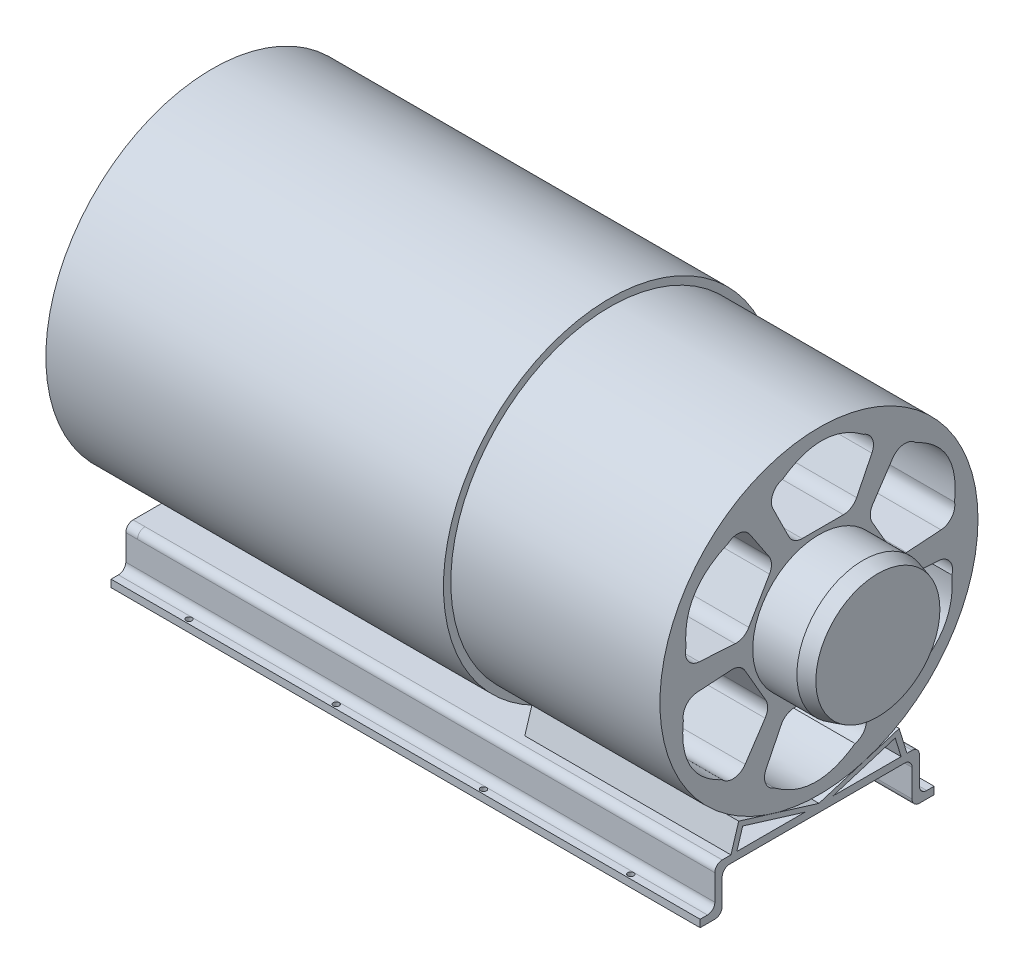
SolidWorks part; units mm, degrees
material "1060 Alloy"
ref_plane "Front Plane" through (0, 0, 0) normal (0, 0, 1) x (1, 0, 0)
ref_plane "Top Plane" through (0, 0, 0) normal (0, 1, 0) x (1, 0, 0)
ref_plane "Right Plane" through (0, 0, 0) normal (1, 0, 0) x (0, 0, -1)
sketch "Sketch1" plane through (0, 0, 0) normal (1, 0, 0) x (0, 0, -1)
  circle A0 centre (0, 0) radius 113
  dimension "D1" = 226
extrude "Boss-Extrude1" add sketch "Sketch1" against normal blind 412
sketch "Sketch2" plane through (0, 0, 0) normal (1, 0, 0) x (0, 0, -1)
  circle A0 centre (0, 0) radius 108
  circle A1 centre (0, 0) radius 113
  dimension "D1" = 216
extrude "Cut-Extrude1" cut sketch "Sketch2" against normal blind 142
sketch "Sketch3" plane through (0, 0, 0) normal (1, 0, 0) x (0, 0, -1)
  circle A0 centre (0, 0) radius 45
  dimension "D1" = 90
extrude "Boss-Extrude2" add sketch "Sketch3" along normal blind 40
chamfer "Chamfer1" distance 10 angle 16 1 edges at (40, 0, -45) first distance on face at (40, 0, -45)
sketch "Sketch4" plane through (0, 0, 0) normal (1, 0, 0) x (0, 0, -1)
  line L0 (-31.2402, 75.8787) -> (-20.392, 53.9645)
  line L1 (-11.43, 48.401) -> (16.6248, 48.401)
  line L2 (25.5919, 53.9748) -> (35.9576, 74.9748)
  line L3 (50.0927, 64.9942) -> (36.5386, 44.6422)
  line L4 (36.2015, 34.0991) -> (50.2288, 9.803)
  line L5 (59.5394, 4.8242) -> (82.9089, 6.3472)
  line L6 (81.333, -10.8845) -> (56.9306, -9.3223)
  line L7 (47.6314, -14.3018) -> (33.6041, -38.5979)
  line L8 (33.9476, -49.1506) -> (46.9513, -68.6276)
  line L9 (31.2402, -75.8787) -> (20.392, -53.9645)
  line L10 (11.43, -48.401) -> (-16.6248, -48.401)
  line L11 (-25.5919, -53.9748) -> (-35.9576, -74.9748)
  line L12 (-50.0927, -64.9942) -> (-36.5386, -44.6422)
  line L13 (-36.2015, -34.0991) -> (-50.2288, -9.803)
  line L14 (-59.5394, -4.8242) -> (-82.9089, -6.3472)
  line L15 (-81.333, 10.8845) -> (-56.9306, 9.3223)
  line L16 (-47.6314, 14.3018) -> (-33.6041, 38.5979)
  line L17 (-33.9476, 49.1506) -> (-46.9513, 68.6276)
  arc A0 (35.9576, 74.9748) -> (30.3376, 88.8243) centre (26.9905, 79.401) ccw
  arc A1 (-31.2402, 75.8787) -> (-24.4733, 90.0713) centre (-22.2782, 80.3152) cw
  arc A2 (-20.392, 53.9645) -> (-11.43, 48.401) centre (-11.43, 58.401) ccw
  arc A3 (16.6248, 48.401) -> (25.5919, 53.9748) centre (16.6248, 58.401) ccw
  arc A4 (50.0927, 64.9942) -> (65.7673, 66.2301) centre (58.4159, 59.4511) cw
  arc A5 (36.5386, 44.6422) -> (36.2015, 34.0991) centre (44.8617, 39.0991) ccw
  arc A6 (50.2288, 9.803) -> (59.5394, 4.8242) centre (58.8891, 14.803) ccw
  arc A7 (82.9089, 6.3472) -> (92.0928, 18.139) centre (82.2586, 16.3261) ccw
  arc A8 (81.333, -10.8845) -> (90.2407, -23.8411) centre (80.6941, -20.8641) cw
  arc A9 (56.9306, -9.3223) -> (47.6314, -14.3018) centre (56.2917, -19.3018) ccw
  arc A10 (33.6041, -38.5979) -> (33.9476, -49.1506) centre (42.2643, -43.5979) ccw
  arc A11 (46.9513, -68.6276) -> (61.7553, -70.6852) centre (55.2681, -63.075) ccw
  arc A12 (31.2402, -75.8787) -> (24.4733, -90.0713) centre (22.2782, -80.3152) cw
  arc A13 (20.392, -53.9645) -> (11.43, -48.401) centre (11.43, -58.401) ccw
  arc A14 (-16.6248, -48.401) -> (-25.5919, -53.9748) centre (-16.6248, -58.401) ccw
  arc A15 (-35.9576, -74.9748) -> (-30.3376, -88.8243) centre (-26.9905, -79.401) ccw
  arc A16 (-50.0927, -64.9942) -> (-65.7673, -66.2301) centre (-58.4159, -59.4511) cw
  arc A17 (-36.5386, -44.6422) -> (-36.2015, -34.0991) centre (-44.8617, -39.0991) ccw
  arc A18 (-50.2288, -9.803) -> (-59.5394, -4.8242) centre (-58.8891, -14.803) ccw
  arc A19 (-82.9089, -6.3472) -> (-92.0928, -18.139) centre (-82.2586, -16.3261) ccw
  arc A20 (-81.333, 10.8845) -> (-90.2407, 23.8411) centre (-80.6941, 20.8641) cw
  arc A21 (-56.9306, 9.3223) -> (-47.6314, 14.3018) centre (-56.2917, 19.3018) ccw
  arc A22 (-33.6041, 38.5979) -> (-33.9476, 49.1506) centre (-42.2643, 43.5979) ccw
  arc A23 (-46.9513, 68.6276) -> (-61.7553, 70.6852) centre (-55.2681, 63.075) ccw
  spline S0 degree 3 poles (30.3376, 88.8243) (20.5234, 96.0661) (2.1757, 102.6494) (-16.0064, 96.0445) (-24.4733, 90.0713) knots 0.076117 0.076117 0.076117 0.076117 0.512929 0.896674 0.896674 0.896674 0.896674
  spline S1 degree 3 poles (92.0928, 18.139) (93.4574, 30.2592) (89.9848, 49.4405) (75.1738, 61.8842) (65.7673, 66.2301) knots 0.076117 0.076117 0.076117 0.076117 0.512929 0.896674 0.896674 0.896674 0.896674
  spline S2 degree 3 poles (61.7553, -70.6852) (72.9339, -65.8069) (87.8091, -53.2089) (91.1802, -34.1603) (90.2407, -23.8411) knots 0.076117 0.076117 0.076117 0.076117 0.512929 0.896674 0.896674 0.896674 0.896674
  spline S3 degree 3 poles (-30.3376, -88.8243) (-20.5234, -96.0661) (-2.1757, -102.6494) (16.0064, -96.0445) (24.4733, -90.0713) knots 0.076117 0.076117 0.076117 0.076117 0.512929 0.896674 0.896674 0.896674 0.896674
  spline S4 degree 3 poles (-92.0928, -18.139) (-93.4574, -30.2592) (-89.9848, -49.4405) (-75.1738, -61.8842) (-65.7673, -66.2301) knots 0.076117 0.076117 0.076117 0.076117 0.512929 0.896674 0.896674 0.896674 0.896674
  spline S5 degree 3 poles (-61.7553, 70.6852) (-72.9339, 65.8069) (-87.8091, 53.2089) (-91.1802, 34.1603) (-90.2407, 23.8411) knots 0.076117 0.076117 0.076117 0.076117 0.512929 0.896674 0.896674 0.896674 0.896674
  point P80 (0, 0)
  dimension "D1" = 10
  dimension "D2" = 6
extrude "Cut-Extrude2" cut sketch "Sketch4" against normal blind 140
sketch "Sketch5" plane through (0, 0, 0) normal (1, 0, 0) x (0, 0, -1)
  line L0 (0, -113) -> (54.4779, -96.2321)
  line L1 (54.4779, -96.2321) -> (59.773, -113.4357)
  line L2 (59.773, -113.4357) -> (55.773, -113.4357)
  line L3 (55.773, -113.4357) -> (51.7735, -100.4415)
  line L4 (51.7735, -100.4415) -> (0, -116.377)
  line L5 (0, -61.5014) -> (0, -90.8439)
  line L6 (-51.7735, -100.4415) -> (0, -116.377)
  line L7 (-55.773, -113.4357) -> (-51.7735, -100.4415)
  line L8 (-59.773, -113.4357) -> (-55.773, -113.4357)
  line L9 (-54.4779, -96.2321) -> (-59.773, -113.4357)
  line L10 (0, -113) -> (-54.4779, -96.2321)
  circle A0 centre (0, 0) radius 113 construction
  dimension "D1" = 4
  dimension "D2" = 18
  dimension "D3" = 57
  dimension "D4" = 54.1704
extrude "Boss-Extrude3" add sketch "Sketch5" against normal blind 140 separate body contours L0 L10 L9 L8 L7 L6 L4 L3 L2 L1 region at (0, -105.7747, -27.5956)
sketch "Sketch7" plane through (0, -113.4357, 0) normal (0, -1, 0) x (1, 0, 0)
  line L0 (0, -108) -> (0, 108) construction
  line L1 (0, 70.7066) -> (-142, 70.7066)
  line L2 (0, 70.7066) -> (0, -68.2082)
  line L3 (0, -68.2082) -> (-142, -68.2082)
  line L4 (-142, 70.7066) -> (-142, -68.2082)
  line L5 (-142, -113) -> (-142, 113) construction
extrude "Boss-Extrude4" add sketch "Sketch7" along normal blind 5
sketch "Sketch8" plane through (0, -118.4357, 0) normal (0, -1, 0) x (1, 0, 0)
  line L0 (0, 70.7066) -> (-142, 70.7066) construction
  line L1 (-142, 70.7066) -> (-392, 70.7066)
  line L2 (-142, 70.7066) -> (-142, -67.7085)
  line L3 (-142, -67.7085) -> (-392, -67.7085)
  line L4 (-392, 70.7066) -> (-392, -67.7085)
  line L5 (-142, -113) -> (-142, 113) construction
  dimension "D1" = 250
extrude "Boss-Extrude5" add sketch "Sketch8" against normal blind 5
sketch "Sketch11" plane through (0, 0, 0) normal (1, 0, 0) x (0, 0, -1)
  line L0 (-65.7066, -113.4357) -> (63.2082, -113.4357)
  line L1 (68.2082, -118.4357) -> (68.2082, -137.0735)
  line L2 (73.2082, -142.0735) -> (78.2082, -142.0735)
  line L3 (78.2082, -142.0735) -> (78.2082, -147.0735)
  line L4 (78.2082, -147.0735) -> (68.2082, -147.0735)
  line L5 (63.2082, -142.0735) -> (63.2082, -123.4357)
  line L6 (68.2082, -118.4357) -> (-70.7066, -118.4357) construction
  line L7 (58.2082, -118.4357) -> (-60.7066, -118.4357)
  line L8 (-65.7066, -123.4357) -> (-65.7066, -140.815)
  line L9 (-70.7066, -145.815) -> (-80.7066, -145.815)
  line L10 (-80.7066, -145.815) -> (-80.7066, -140.815)
  line L11 (-80.7066, -140.815) -> (-75.7066, -140.815)
  line L12 (-70.7066, -135.815) -> (-70.7066, -118.4357)
  arc A0 (63.2082, -113.4357) -> (68.2082, -118.4357) centre (63.2082, -118.4357) cw
  arc A1 (63.2082, -123.4357) -> (58.2082, -118.4357) centre (58.2082, -123.4357) ccw
  arc A2 (-60.7066, -118.4357) -> (-65.7066, -123.4357) centre (-60.7066, -123.4357) ccw
  arc A3 (-65.7066, -113.4357) -> (-70.7066, -118.4357) centre (-65.7066, -118.4357) ccw
  arc A4 (-65.7066, -140.815) -> (-70.7066, -145.815) centre (-70.7066, -140.815) cw
  arc A5 (-75.7066, -140.815) -> (-70.7066, -135.815) centre (-75.7066, -135.815) ccw
  arc A6 (68.2082, -137.0735) -> (73.2082, -142.0735) centre (73.2082, -137.0735) ccw
  arc A7 (68.2082, -147.0735) -> (63.2082, -142.0735) centre (68.2082, -142.0735) cw
  point P18 (68.2082, -113.4357)
  point P21 (63.2082, -118.4357)
  point P24 (-65.7066, -118.4357)
  point P27 (-70.7066, -113.4357)
  point P30 (-65.7066, -145.815)
  point P37 (63.2082, -147.0735)
  dimension "D7" = 5
  dimension "D1" = 15
  dimension "D2" = 15
  dimension "D3" = 5
  dimension "D4" = 5
  dimension "D5" = 5
  dimension "D6" = 5
extrude "Boss-Extrude6" add sketch "Sketch11" against normal blind 400
fillet "Fillet1" radius 5 1 edges at (-71, -113.4357, -68.2082)
fillet "Fillet2" radius 5 1 edges at (-196, -113.4357, 70.7066)
sketch "Sketch12" plane through (0, -147.0735, 0) normal (0, -1, 0) x (1, 0, 0)
  line L0 (-400, -78.2082) -> (-400, -68.2082)
  circle A0 centre (-350, -73.2082) radius 2
  circle A1 centre (-250, -73.2082) radius 2
  circle A2 centre (-150, -73.2082) radius 2
  circle A3 centre (-50, -73.2082) radius 2
  circle A4 centre (-250, 77.7918) radius 2
  circle A5 centre (-150, 77.7918) radius 2
  circle A6 centre (-50, 77.7918) radius 2
  circle A7 centre (-350, 77.7918) radius 2
  point P2 (-400, -73.2082)
  dimension "D1" = 4
  dimension "D2" = 50
  dimension "D5" = 151
  dimension "D3" = 4
  dimension "D4" = 2
extrude "Cut-Extrude3" cut sketch "Sketch12" against normal up to surface (6.2585 mm away) contours A0 | A1 | A2 | A3 | A7 | A4 | A5 | A6 region at (-350, -147.0735, -73.2082) region at (-250, -147.0735, -73.2082) region at (-150, -147.0735, -73.2082) region at (-50, -147.0735, -73.2082) region at (-250, -147.0735, 77.7918) region at (-150, -147.0735, 77.7918) region at (-50, -147.0735, 77.7918) region at (-350, -147.0735, 77.7918) up to face at (-200, -140.815, 78.2066)
